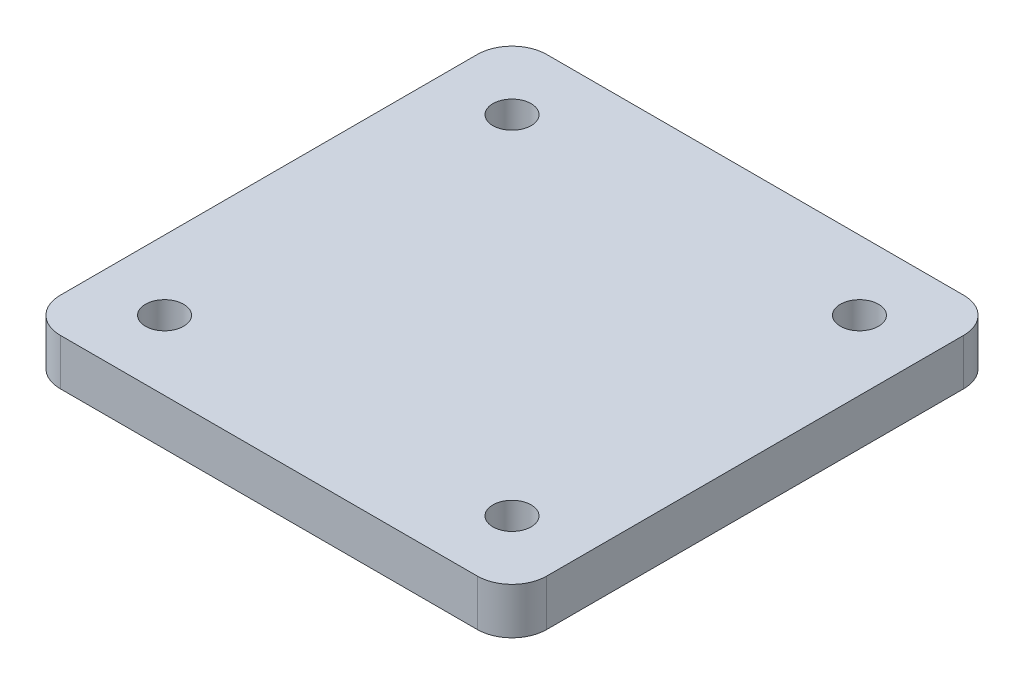
SolidWorks part; units mm, degrees
ref_plane "前视基准面" through (0, 0, 0) normal (0, 0, 1) x (1, 0, 0)
ref_plane "上视基准面" through (0, 0, 0) normal (0, 1, 0) x (1, 0, 0)
ref_plane "右视基准面" through (0, 0, 0) normal (1, 0, 0) x (0, 0, -1)
other "Configuration Table"
sketch "草图1" plane through (0, 0, 0) normal (0, 0, 1) x (1, 0, 0)
  line L0 (0, 0) -> (42, 0)
  line L1 (42, 0) -> (42, 4)
  line L2 (42, 4) -> (0, 4)
  line L3 (0, 4) -> (0, 0)
  dimension "width" = 42
  dimension "height" = 4
extrude "BlockExtrude" add sketch "草图1" along normal blind 42
fillet "Fillet" radius 3 4 edges at (0, 2, 0) (42, 2, 0) (0, 2, 42) (42, 2, 42) tangent propagation no
sketch "草图2" plane through (0, 4, 0) normal (0, 1, 0) x (1, 0, 0)
  circle A0 centre (6, -6) radius 1.65
  dimension "diameter" = 3.3
  dimension "x" = 6
  dimension "y" = 6
extrude "Mount_hole" cut sketch "草图2" against normal through all
sketch "草图3" plane through (0, 4, 0) normal (0, 1, 0) x (1, 0, 0)
  circle A0 centre (6, -36) radius 1.65
  dimension "diameter" = 3.3
  dimension "x" = 6
  dimension "y" = 36
extrude "切除-拉伸2" cut sketch "草图3" against normal through all
sketch "草图4" plane through (0, 4, 0) normal (0, 1, 0) x (1, 0, 0)
  circle A0 centre (36, -6) radius 1.65
  dimension "diameter" = 3.3
  dimension "x" = 36
  dimension "y" = 6
extrude "切除-拉伸3" cut sketch "草图4" against normal through all
sketch "草图5" plane through (0, 4, 0) normal (0, 1, 0) x (1, 0, 0)
  circle A0 centre (36, -36) radius 1.65
  dimension "diameter" = 3.3
  dimension "x" = 36
  dimension "y" = 36
extrude "切除-拉伸4" cut sketch "草图5" against normal through all
